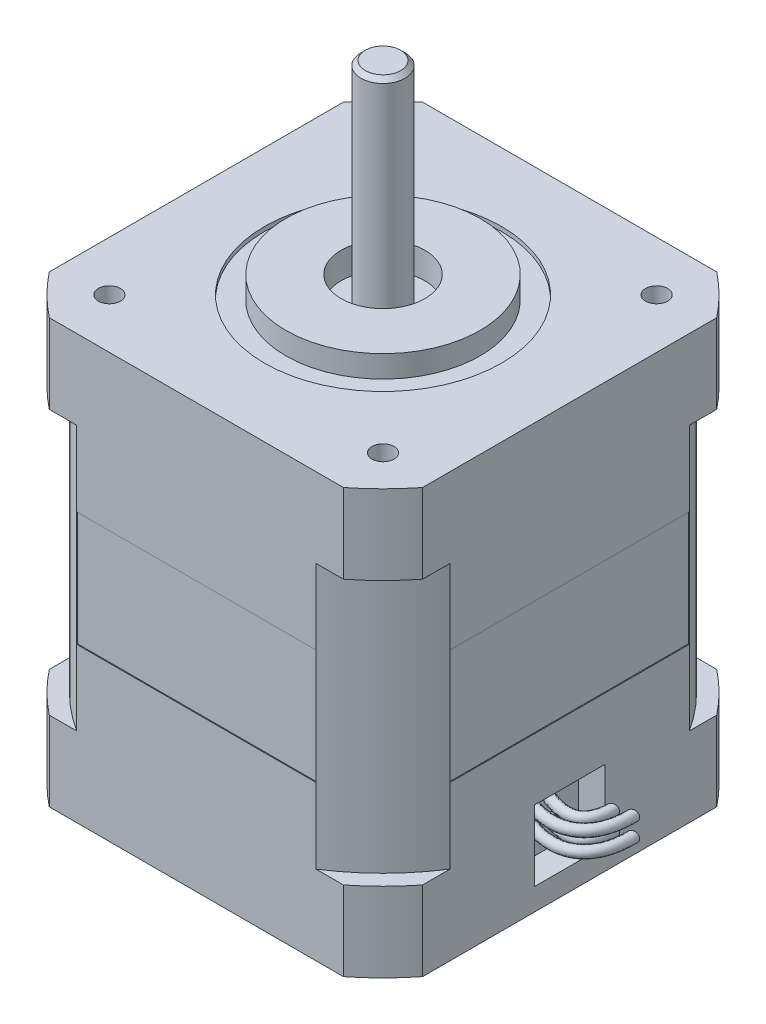
SolidWorks part; units mm, degrees
ref_plane "Front Plane" through (0, 0, 0) normal (0, 0, 1) x (1, 0, 0)
ref_plane "Top Plane" through (0, 0, 0) normal (0, 1, 0) x (1, 0, 0)
ref_plane "Right Plane" through (0, 0, 0) normal (1, 0, 0) x (0, 0, -1)
sketch "Sketch1" plane through (0, 0, 0) normal (0, 1, 0) x (1, 0, 0)
  line L0 (0, -21.15) -> (0, 21.15) construction
  line L1 (-21.15, 16.6623) -> (-21.15, -16.6623)
  line L2 (-16.6623, -21.15) -> (16.6623, -21.15)
  line L3 (21.15, -16.6623) -> (21.15, 16.6623)
  line L4 (16.6623, 21.15) -> (-16.6623, 21.15)
  line L5 (-21.15, 0) -> (21.15, 0) construction
  arc A0 (-21.15, 16.6623) -> (-16.6623, 21.15) centre (0, 0) cw
  arc A1 (16.6623, 21.15) -> (21.15, 16.6623) centre (0, 0) cw
  arc A2 (21.15, -16.6623) -> (16.6623, -21.15) centre (0, 0) cw
  arc A3 (-21.15, -16.6623) -> (-16.6623, -21.15) centre (0, 0) ccw
  dimension "D3" = 26.925
  dimension "D1" = 42.3
  dimension "D2" = 42.3
extrude "Boss-Extrude2" add sketch "Sketch1" along normal blind 48
sketch "Sketch3" plane through (0, 0, 0) normal (0, 0, 1) x (1, 0, 0)
  line L0 (0, -2.0131) -> (0, 34.8611) construction
  line L1 (-30.125, 39) -> (-25.125, 39)
  line L2 (-30.125, 39) -> (-30.125, 9)
  line L3 (-30.125, 9) -> (-25.125, 9)
  line L4 (-25.125, 39) -> (-25.125, 9)
  line L5 (21.15, 24) -> (-21.15, 24) construction
  line L6 (21.15, 48) -> (21.15, 0) construction
  line L7 (-21.15, 48) -> (-21.15, 0) construction
  point P13 (-25.125, 24)
  dimension "D1" = 30
  dimension "D2" = 25.125
  dimension "D3" = 5
revolve "Cut-Revolve1" cut sketch "Sketch3" angle 360 about L0
sketch "Sketch4" plane through (0, 48, 0) normal (0, 1, 0) x (1, 0, 0)
  circle A0 centre (0, 0) radius 13.425
  dimension "D1" = 26.85
extrude "Cut-Extrude1" cut sketch "Sketch4" against normal blind 0.5
sketch "Sketch5" plane through (0, 47.5, 0) normal (0, 1, 0) x (1, 0, 0)
  circle A0 centre (0, 0) radius 11
  dimension "D1" = 22
extrude "Boss-Extrude3" add sketch "Sketch5" along normal blind 2.5
sketch "Sketch6" plane through (0, 50, 0) normal (0, 1, 0) x (1, 0, 0)
  circle A0 centre (0, 0) radius 4.75
  dimension "D1" = 9.5
extrude "Cut-Extrude2" cut sketch "Sketch6" against normal blind 3
sketch "Sketch7" plane through (0, 47, 0) normal (0, 1, 0) x (1, 0, 0)
  circle A0 centre (0, 0) radius 2.5
  dimension "D1" = 5
extrude "Boss-Extrude4" add sketch "Sketch7" along normal blind 24
chamfer "Chamfer1" distance 0.5 angle 45 1 edges at (0, 71, 2.5)
sketch "Sketch8" plane through (0, 0, 0) normal (0, -1, 0) x (1, 0, 0)
  circle A0 centre (0, 0) radius 4.5
  dimension "D1" = 9
extrude "Cut-Extrude3" cut sketch "Sketch8" against normal blind 3
sketch "Sketch9" plane through (0, 48, 0) normal (0, 1, 0) x (1, 0, 0)
  line L0 (-15.5, 15.5) -> (15.5, 15.5) construction
  line L1 (15.5, 15.5) -> (15.5, -15.5) construction
  line L2 (15.5, -15.5) -> (-15.5, -15.5) construction
  line L3 (-15.5, -15.5) -> (-15.5, 15.5) construction
  point P2 (-15.5, 0)
  point P5 (0, 15.5)
  dimension "D1" = 31
  dimension "D2" = 31
hole_wizard "M3x0.5 Tapped Hole1" positions "Sketch11" profile "Sketch10" tap size "M3x0.5" standard "ANSI Metric"
sketch "Sketch11" plane through (0, 48, 0) normal (0, 1, 0) x (1, 0, 0)
  point P0 (-15.5, -15.5)
  point P3 (-15.5, 15.5)
  point P6 (15.5, 15.5)
  point P9 (15.5, -15.5)
sketch "Sketch10" plane through (-15.5, 48, 15.5) normal (1, 0, 0) x (0, 0, 1)
  line L0 (0, 0) -> (0, 5.2511)
  line L1 (0, 5.2511) -> (1.25, 4.5)
  line L2 (1.25, 4.5) -> (1.25, 0)
  line L5 (1.25, 0) -> (0, 0)
  line L10 (0, 5.2511) -> (-1.25, 4.5) construction
  line L11 (0, -6.35) -> (0, 107.95) construction
  dimension "Tap Drill Dia." = 2.5
  dimension "Tap Drill Depth" = 4.5
  dimension "Drill Angle" = 118
sketch "Sketch12" plane through (21.15, 0, 0) normal (1, 0, 0) x (0, 0, -1)
  line L0 (-16.6623, 0) -> (16.6623, 0) construction
  line L1 (-4, 10.5) -> (4, 10.5)
  line L2 (-4, 10.5) -> (-4, 2.5)
  line L3 (-4, 2.5) -> (4, 2.5)
  line L4 (4, 10.5) -> (4, 2.5)
  point P4 (0, 2.5)
  dimension "D1" = 8
  dimension "D2" = 8
  dimension "D3" = 2.5
extrude "Cut-Extrude4" cut sketch "Sketch12" against normal blind 3
sketch "Sketch13" plane through (18.15, 0, 0) normal (1, 0, 0) x (0, 0, -1)
  circle A0 centre (-1.1125, 7.415) radius 0.6
  circle A1 centre (0.707, 7.415) radius 0.6
  circle A2 centre (-1.1125, 5.3322) radius 0.6
  circle A3 centre (0.707, 5.3322) radius 0.6
  dimension "D1" = 1.2
sketch "Sketch14" plane through (0, 0, 0) normal (0, 1, 0) x (1, 0, 0)
  spline S0 degree 2 poles (17.6767, 0) (23.6461, -2.3668) (23.7984, 3.3576) knots 0 0 0 1 1 1
sweep "Sweep2" add profiles "Sketch13" path "Sketch14"
sketch "Sketch15" plane through (0, 0, -21.15) normal (0, 0, -1) x (-1, 0, 0)
  line L0 (-13.5626, 9) -> (-13.5626, 39) construction
  line L1 (-13.5626, 30.5) -> (13.5626, 30.5)
  line L2 (-13.5626, 30.5) -> (-13.5626, 17.5)
  line L3 (-13.5626, 17.5) -> (13.5626, 17.5)
  line L4 (13.5626, 30.5) -> (13.5626, 17.5)
  line L5 (13.5626, 39) -> (13.5626, 9) construction
  point P8 (-13.5626, 24)
  point P9 (-13.5626, 24)
  dimension "D1" = 13
extrude "Cut-Extrude5" cut sketch "Sketch15" against normal blind 0.1
ref_axis "Axis1" through (0, 0, 0) along (0, 1, 0)
pattern_circular "CirPattern1" count 4 over 360 about axis through (0, 0, 0) along (0, 1, 0) of "Cut-Extrude5"
